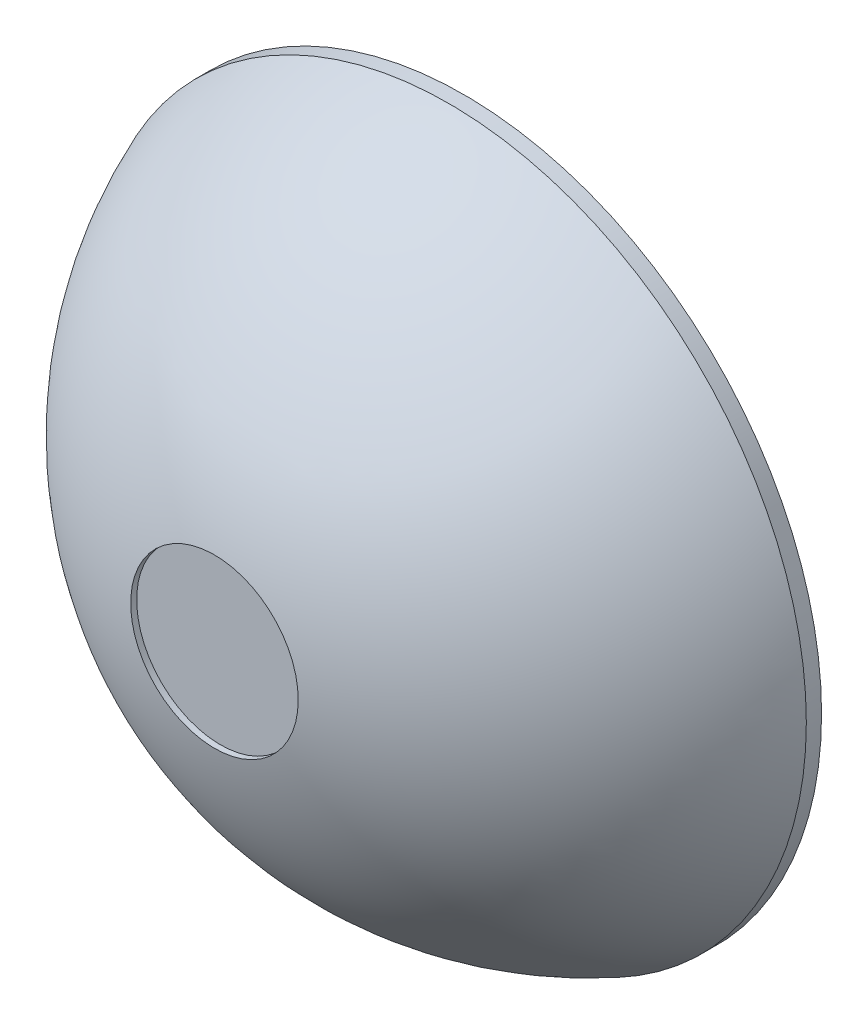
SolidWorks part; units mm, degrees
ref_plane "Front Plane" through (0, 0, 0) normal (0, 0, 1) x (1, 0, 0)
ref_plane "Top Plane" through (0, 0, 0) normal (0, 1, 0) x (1, 0, 0)
ref_plane "Right Plane" through (0, 0, 0) normal (1, 0, 0) x (0, 0, -1)
sketch "Sketch3" plane through (0, 0, 0) normal (0, 0, 1) x (1, 0, 0)
  circle A0 centre (0, 0) radius 17.8816
  dimension "D1" = 35.7632
extrude "Boss-Extrude2" add sketch "Sketch3" along normal blind 0.762
dome "Dome1" faces to dome 1 distance 12.192 reverse direction no elliptical dome no face at (17.8816, 0, 0.762) parameters "D1"=12.192
ref_plane "Plane1" through (0, 0, 12.192) normal (0, 0, 1) x (1, 0, 0)
sketch "Sketch4" plane through (0, 0, 12.192) normal (0, 0, 1) x (1, 0, 0)
  circle A1 centre (0, 0) radius 4.191
extrude "Cut-Extrude1" cut sketch "Sketch4" along normal blind 1.016
sketch "Sketch5" plane through (0, 0, 0) normal (0, 0, -1) x (-1, 0, 0)
  circle A0 centre (0, 0) radius 17.3736
  dimension "D1" = 34.7472
extrude "Cut-Extrude2" cut sketch "Sketch5" against normal blind 1.27
shell "Shell3" thickness 0.508 removed face at (-17.3736, 0, 1.27)
